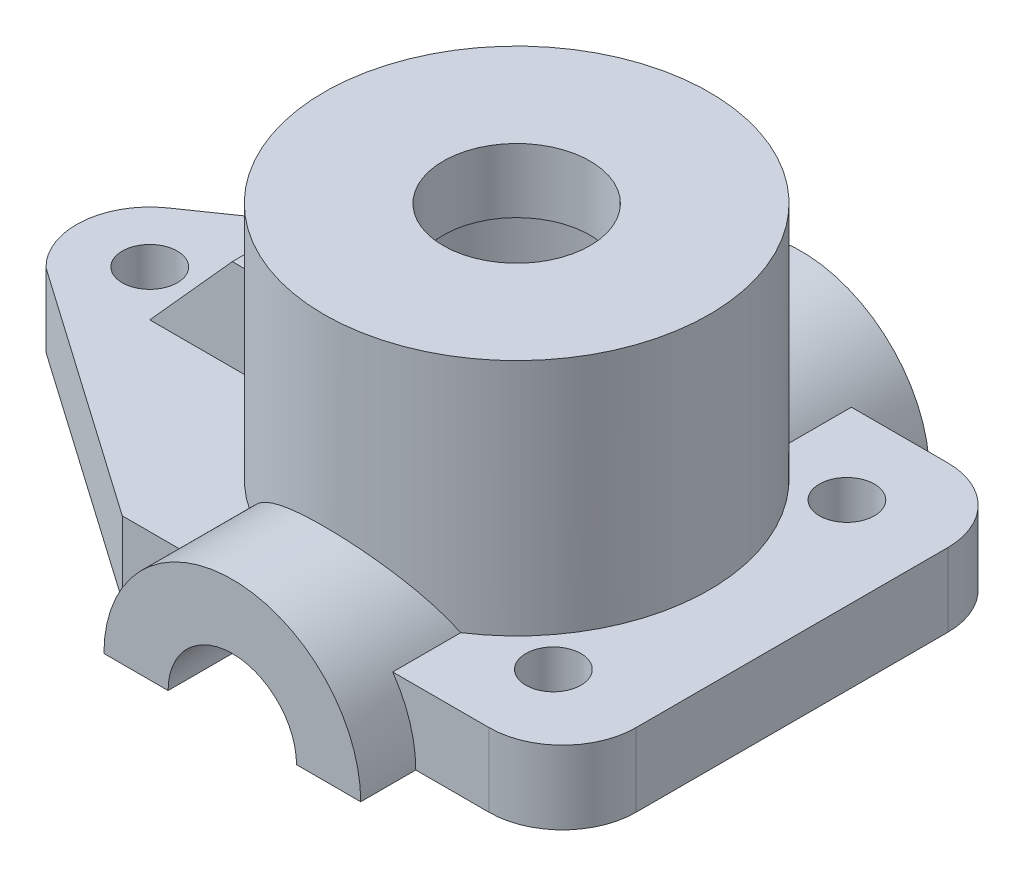
SolidWorks part; units mm, degrees
ref_plane "前视基准面" through (0, 0, 0) normal (0, 0, 1) x (1, 0, 0)
ref_plane "上视基准面" through (0, 0, 0) normal (0, 1, 0) x (1, 0, 0)
ref_plane "右视基准面" through (0, 0, 0) normal (1, 0, 0) x (0, 0, -1)
sketch "草图1" plane through (0, 0, 0) normal (0, 0, 1) x (1, 0, 0)
  line L0 (-14, 0) -> (14, 0)
  arc A0 (14, 0) -> (-14, 0) centre (0, 0) ccw
extrude "凸台-拉伸1" add sketch "草图1" along normal blind 31 and the other way blind 31
sketch "草图2" plane through (0, 0, 0) normal (0, 1, 0) x (1, 0, 0)
  circle A0 centre (0, 0) radius 21
extrude "凸台-拉伸2" add sketch "草图2" along normal blind 34
sketch "草图3" plane through (0, 0, 0) normal (0, 1, 0) x (1, 0, 0)
  line L0 (-18.7, 0) -> (18.7, 0) construction
  line L1 (0, 25) -> (0, -25)
  line L2 (0, -18.7) -> (0, 18.7) construction
  line L5 (0, 25) -> (-18, 25)
  line L6 (0, -25) -> (-18, -25)
  line L7 (-18, 25) -> (-44.5602, 6.573)
  line L8 (-18, -25) -> (-45.5822, -5.7306)
  arc A0 (-44.5602, 6.573) -> (-45.5822, -5.7306) centre (-40, 0) ccw
  point P11 (0, 0)
  dimension "D2" = 18
  dimension "D4" = 16
  dimension "D1" = 40
  dimension "D3" = 50
extrude "凸台-拉伸3" add sketch "草图3" along normal blind 8
sketch "草图4" plane through (0, 0, 0) normal (0, 1, 0) x (1, 0, 0)
  line L0 (0, -25) -> (0, 25)
  line L1 (0, -18.7) -> (0, 18.7) construction
  line L2 (0, 25) -> (22, 25)
  line L3 (30, 17) -> (30, -17)
  line L4 (22, -25) -> (0, -25)
  arc A0 (22, -25) -> (30, -17) centre (22, -17) ccw
  arc A2 (30, 17) -> (22, 25) centre (22, 17) ccw
  point P7 (0, 0)
  point P9 (30, 25)
  dimension "D4" = 8
  dimension "D5" = 8
  dimension "D1" = 25
  dimension "D2" = 50
  dimension "D3" = 30
extrude "凸台-拉伸4" add sketch "草图4" along normal blind 8
sketch "草图5" plane through (0, 0, 0) normal (0, 0, 1) x (1, 0, 0)
  line L0 (-16.6361, 8) -> (-35, 8)
  line L1 (-18, 8) -> (-11.4891, 8) construction
  line L2 (-45.5822, 8) -> (-18, 8) construction
  line L3 (-35, 8) -> (-26, 18)
  line L4 (-26, 18) -> (-16.6361, 18)
  line L5 (-16.6361, 18) -> (-16.6361, 8)
  line L7 (0, -18.7) -> (0, 18.7) construction
  dimension "D1" = 26
  dimension "D2" = 35
  dimension "D3" = 10
extrude "凸台-拉伸5" add sketch "草图5" along normal blind 5 and the other way blind 5
sketch "草图6" plane through (0, 34, 0) normal (0, 1, 0) x (1, 0, 0)
  circle A0 centre (0, 0) radius 8
  dimension "D1" = 16
extrude "切除-拉伸1" cut sketch "草图6" against normal blind 7
sketch "草图7" plane through (0, 27, 0) normal (0, 1, 0) x (1, 0, 0)
  circle A0 centre (0, 0) radius 15
  dimension "D1" = 30
extrude "切除-拉伸2" cut sketch "草图7" against normal through all
sketch "草图8" plane through (0, 0, 31) normal (0, 0, 1) x (1, 0, 0)
  circle A0 centre (0, 0) radius 7
  dimension "D1" = 14
extrude "切除-拉伸3" cut sketch "草图8" against normal through all
sketch "草图9" plane through (0, 8, 0) normal (0, 1, 0) x (1, 0, 0)
  line L0 (-18.9545, 0) -> (18.9545, 0) construction
  line L1 (0, -18.9545) -> (0, 18.9545) construction
  circle A0 centre (-40, 0) radius 3
  circle A1 centre (20, 16) radius 3
  circle A4 centre (20, -16) radius 3
  point P11 (18.2659, 14.7696)
  dimension "D1" = 6
  dimension "D3" = 6
  dimension "D4" = 20
  dimension "D5" = 16
  dimension "D2" = 40
extrude "切除-拉伸4" cut sketch "草图9" against normal through all
